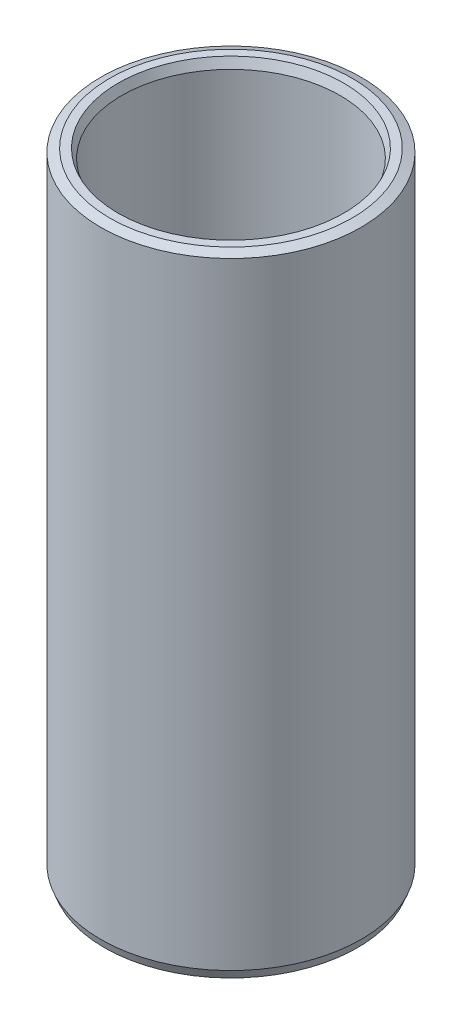
SolidWorks part; units mm, degrees
ref_plane "Front Plane" through (0, 0, 0) normal (0, 0, 1) x (1, 0, 0)
ref_plane "Top Plane" through (0, 0, 0) normal (0, 1, 0) x (1, 0, 0)
ref_plane "Right Plane" through (0, 0, 0) normal (1, 0, 0) x (0, 0, -1)
sketch "Sketch1" plane through (0, 0, 0) normal (0, 1, 0) x (1, 0, 0)
  circle A0 centre (0, 0) radius 55
  dimension "SLEEVE_OD" = 110
extrude "Boss-Extrude1" add sketch "Sketch1" along normal blind 265.8756
sketch "Sketch2" plane through (0, 0, 0) normal (0, 1, 0) x (1, 0, 0)
  circle A0 centre (0, 0) radius 46.1508
  dimension "BORE_D" = 92.3016
extrude "Cut-Extrude1" cut sketch "Sketch2" along normal through all
chamfer "Chamfer1" distance 1.5071 angle 68.318 4 edges at (0, 265.8756, 46.1508) (0, 0, 46.1508) (0, 0, 55) (0, 265.8756, 55) first distance on face at (0, 265.8756, 46.1508) first distance on face at (0, 0, 46.1508) first distance on face at (0, 265.8756, 55)
